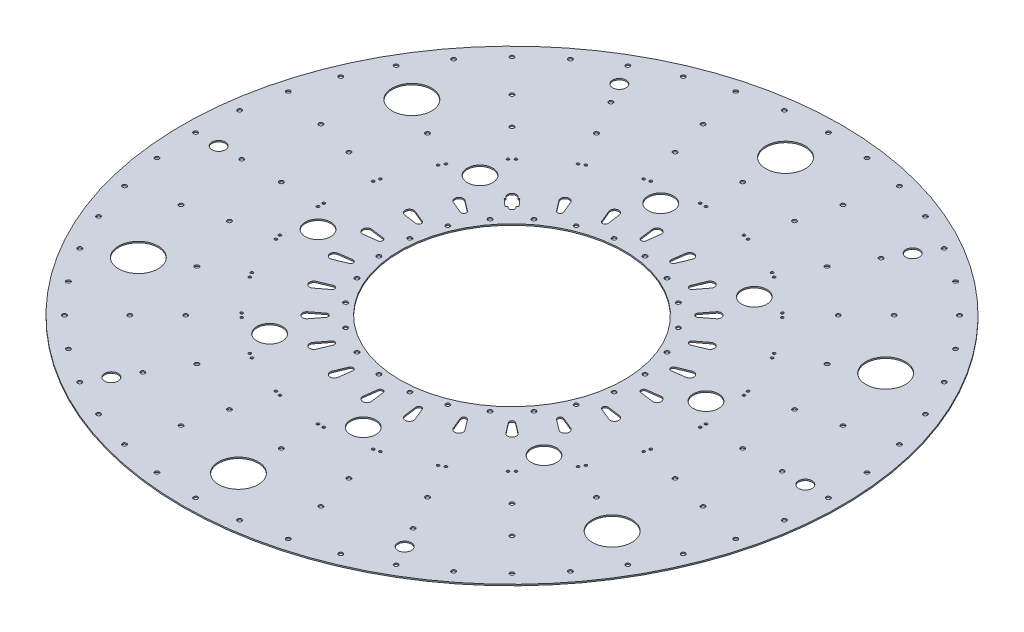
SolidWorks part; units mm, degrees
ref_plane "Front Plane" through (0, 0, 0) normal (0, 0, 1) x (1, 0, 0)
ref_plane "Top Plane" through (0, 0, 0) normal (0, 1, 0) x (1, 0, 0)
ref_plane "Right Plane" through (0, 0, 0) normal (1, 0, 0) x (0, 0, -1)
sketch "Sketch2" plane through (0, 0, 0) normal (0, 1, 0) x (1, 0, 0)
  line L0 (0, 0) -> (0, 231.6511) construction
  line L1 (-5.5, 109.8624) -> (-5, 99.8749) construction
  line L2 (5.5, 109.8624) -> (5, 99.8749) construction
  line L3 (-4.1887, 108.6693) -> (-3.8137, 101.1782) construction
  line L4 (4.1887, 108.6693) -> (3.8137, 101.1782) construction
  line L5 (24.0797, 106.0506) -> (22.5031, 98.7176) construction
  line L6 (32.1717, 103.8824) -> (29.8706, 96.7435) construction
  line L7 (50.7071, 96.2047) -> (47.2863, 89.5297) construction
  line L8 (57.9622, 92.016) -> (53.8918, 85.716) construction
  line L9 (73.8789, 79.8027) -> (68.8471, 74.2404) construction
  line L10 (79.8027, 73.8789) -> (74.2404, 68.8471) construction
  line L11 (92.016, 57.9622) -> (85.716, 53.8918) construction
  line L12 (96.2047, 50.7071) -> (89.5297, 47.2863) construction
  line L13 (103.8824, 32.1717) -> (96.7435, 29.8706) construction
  line L14 (106.0506, 24.0797) -> (98.7176, 22.5031) construction
  line L15 (108.6693, 4.1887) -> (101.1782, 3.8137) construction
  line L16 (108.6693, -4.1887) -> (101.1782, -3.8137) construction
  line L17 (106.0506, -24.0797) -> (98.7176, -22.5031) construction
  line L18 (103.8824, -32.1717) -> (96.7435, -29.8706) construction
  line L19 (96.2047, -50.7071) -> (89.5297, -47.2863) construction
  line L20 (92.016, -57.9622) -> (85.716, -53.8918) construction
  line L21 (79.8027, -73.8789) -> (74.2404, -68.8471) construction
  line L22 (73.8789, -79.8027) -> (68.8471, -74.2404) construction
  line L23 (57.9622, -92.016) -> (53.8918, -85.716) construction
  line L24 (50.7071, -96.2047) -> (47.2863, -89.5297) construction
  line L25 (32.1717, -103.8824) -> (29.8706, -96.7435) construction
  line L26 (24.0797, -106.0506) -> (22.5031, -98.7176) construction
  line L27 (4.1887, -108.6693) -> (3.8137, -101.1782) construction
  line L28 (-4.1887, -108.6693) -> (-3.8137, -101.1782) construction
  line L29 (-24.0797, -106.0506) -> (-22.5031, -98.7176) construction
  line L30 (-32.1717, -103.8824) -> (-29.8706, -96.7435) construction
  line L31 (-50.7071, -96.2047) -> (-47.2863, -89.5297) construction
  line L32 (-57.9622, -92.016) -> (-53.8918, -85.716) construction
  line L33 (-73.8789, -79.8027) -> (-68.8471, -74.2404) construction
  line L34 (-79.8027, -73.8789) -> (-74.2404, -68.8471) construction
  line L35 (-92.016, -57.9622) -> (-85.716, -53.8918) construction
  line L36 (-96.2047, -50.7071) -> (-89.5297, -47.2863) construction
  line L37 (-103.8824, -32.1717) -> (-96.7435, -29.8706) construction
  line L38 (-106.0506, -24.0797) -> (-98.7176, -22.5031) construction
  line L39 (-108.6693, -4.1887) -> (-101.1782, -3.8137) construction
  line L40 (-108.6693, 4.1887) -> (-101.1782, 3.8137) construction
  line L41 (-106.0506, 24.0797) -> (-98.7176, 22.5031) construction
  line L42 (-103.8824, 32.1717) -> (-96.7435, 29.8706) construction
  line L43 (-96.2047, 50.7071) -> (-89.5297, 47.2863) construction
  line L44 (-92.016, 57.9622) -> (-85.716, 53.8918) construction
  line L45 (-79.8027, 73.8789) -> (-74.2404, 68.8471)
  line L46 (-73.8789, 79.8027) -> (-68.8471, 74.2404)
  line L47 (-57.9622, 92.016) -> (-53.8918, 85.716) construction
  line L48 (-50.7071, 96.2047) -> (-47.2863, 89.5297) construction
  line L49 (-32.1717, 103.8824) -> (-29.8706, 96.7435) construction
  line L50 (-24.0797, 106.0506) -> (-22.5031, 98.7176) construction
  line L51 (0, 0) -> (192.6907, 111.25) construction
  line L52 (-45, -77.9423) -> (-80.1604, -138.8419) construction
  line L53 (3.277, 109.5687) -> (1.9829, 99.7391)
  line L54 (-3.277, 109.5687) -> (-1.9829, 99.7391)
  line L55 (31.5238, 104.9871) -> (27.7297, 95.8273)
  line L56 (25.1931, 106.6834) -> (23.899, 96.8538)
  line L57 (57.6223, 93.2508) -> (51.5868, 85.3851)
  line L58 (51.9464, 96.5278) -> (48.1523, 87.368)
  line L59 (79.7939, 75.1596) -> (71.9283, 69.1241)
  line L60 (75.1596, 79.7939) -> (69.1241, 71.9283)
  line L61 (96.5278, 51.9464) -> (87.368, 48.1523)
  line L62 (93.2508, 57.6223) -> (85.3851, 51.5868)
  line L63 (106.6834, 25.1931) -> (96.8538, 23.899)
  line L64 (104.9871, 31.5238) -> (95.8273, 27.7297)
  line L65 (109.5687, -3.277) -> (99.7391, -1.9829)
  line L66 (109.5687, 3.277) -> (99.7391, 1.9829)
  line L67 (104.9871, -31.5238) -> (95.8273, -27.7297)
  line L68 (106.6834, -25.1931) -> (96.8538, -23.899)
  line L69 (93.2508, -57.6223) -> (85.3851, -51.5868)
  line L70 (96.5278, -51.9464) -> (87.368, -48.1523)
  line L71 (75.1596, -79.7939) -> (69.1241, -71.9283)
  line L72 (79.7939, -75.1596) -> (71.9283, -69.1241)
  line L73 (51.9464, -96.5278) -> (48.1523, -87.368)
  line L74 (57.6223, -93.2508) -> (51.5868, -85.3851)
  line L75 (25.1931, -106.6834) -> (23.899, -96.8538)
  line L76 (31.5238, -104.9871) -> (27.7297, -95.8273)
  line L77 (-3.277, -109.5687) -> (-1.9829, -99.7391)
  line L78 (3.277, -109.5687) -> (1.9829, -99.7391)
  line L79 (-31.5238, -104.9871) -> (-27.7297, -95.8273)
  line L80 (-25.1931, -106.6834) -> (-23.899, -96.8538)
  line L81 (-57.6223, -93.2508) -> (-51.5868, -85.3851)
  line L82 (-51.9464, -96.5278) -> (-48.1523, -87.368)
  line L83 (-79.7939, -75.1596) -> (-71.9283, -69.1241)
  line L84 (-75.1596, -79.7939) -> (-69.1241, -71.9283)
  line L85 (-96.5278, -51.9464) -> (-87.368, -48.1523)
  line L86 (-93.2508, -57.6223) -> (-85.3851, -51.5868)
  line L87 (-106.6834, -25.1931) -> (-96.8538, -23.899)
  line L88 (-104.9871, -31.5238) -> (-95.8273, -27.7297)
  line L89 (-109.5687, 3.277) -> (-99.7391, 1.9829)
  line L90 (-109.5687, -3.277) -> (-99.7391, -1.9829)
  line L91 (-104.9871, 31.5238) -> (-95.8273, 27.7297)
  line L92 (-106.6834, 25.1931) -> (-96.8538, 23.899)
  line L93 (-93.2508, 57.6223) -> (-85.3851, 51.5868)
  line L94 (-96.5278, 51.9464) -> (-87.368, 48.1523)
  line L95 (-75.1596, 79.7939) -> (-69.1241, 71.9283)
  line L96 (-79.7939, 75.1596) -> (-71.9283, 69.1241)
  line L97 (-51.9464, 96.5278) -> (-48.1523, 87.368)
  line L98 (-57.6223, 93.2508) -> (-51.5868, 85.3851)
  line L99 (-25.1931, 106.6834) -> (-23.899, 96.8538)
  line L100 (-31.5238, 104.9871) -> (-27.7297, 95.8273)
  line L101 (0, 0) -> (0, 90) construction
  line L102 (0, 0) -> (-11.7474, 89.23) construction
  circle A0 centre (0, 0) radius 250 construction
  circle A1 centre (0, 0) radius 145 construction
  arc A2 (5.5, 109.8624) -> (-5.5, 109.8624) centre (0, 0) ccw construction
  arc A3 (5, 99.8749) -> (-5, 99.8749) centre (0, 0) ccw construction
  circle A4 centre (0, 0) radius 95 construction
  arc A5 (-5, 99.8749) -> (5, 99.8749) centre (0, 0) ccw construction
  arc A6 (-5.5, 109.8624) -> (5.5, 109.8624) centre (0, 0) ccw construction
  arc A7 (3.8137, 101.1782) -> (-3.8137, 101.1782) centre (0, 0) ccw construction
  arc A8 (4.1887, 108.6693) -> (-4.1887, 108.6693) centre (0, 0) ccw construction
  arc A9 (29.8706, 96.7435) -> (22.5031, 98.7176) centre (0, 0) ccw construction
  arc A10 (32.1717, 103.8824) -> (24.0797, 106.0506) centre (0, 0) ccw construction
  arc A11 (53.8918, 85.716) -> (47.2863, 89.5297) centre (0, 0) ccw construction
  arc A12 (57.9622, 92.016) -> (50.7071, 96.2047) centre (0, 0) ccw construction
  arc A13 (74.2404, 68.8471) -> (68.8471, 74.2404) centre (0, 0) ccw construction
  arc A14 (79.8027, 73.8789) -> (73.8789, 79.8027) centre (0, 0) ccw construction
  arc A15 (89.5297, 47.2863) -> (85.716, 53.8918) centre (0, 0) ccw construction
  arc A16 (96.2047, 50.7071) -> (92.016, 57.9622) centre (0, 0) ccw construction
  arc A17 (98.7176, 22.5031) -> (96.7435, 29.8706) centre (0, 0) ccw construction
  arc A18 (106.0506, 24.0797) -> (103.8824, 32.1717) centre (0, 0) ccw construction
  arc A19 (101.1782, -3.8137) -> (101.1782, 3.8137) centre (0, 0) ccw construction
  arc A20 (108.6693, -4.1887) -> (108.6693, 4.1887) centre (0, 0) ccw construction
  arc A21 (96.7435, -29.8706) -> (98.7176, -22.5031) centre (0, 0) ccw construction
  arc A22 (103.8824, -32.1717) -> (106.0506, -24.0797) centre (0, 0) ccw construction
  circle A23 centre (0, 240) radius 1.6
  circle A31 centre (0, 0) radius 75.5
  circle A32 centre (0, 90) radius 1.6 construction
  circle A33 centre (0, 40) radius 1.6 construction
  circle A34 centre (10.3528, 38.637) radius 1.6 construction
  circle A35 centre (23.2937, 86.9333) radius 1.6 construction
  circle A36 centre (20, 34.641) radius 1.6 construction
  circle A37 centre (45, 77.9423) radius 1.6 construction
  circle A38 centre (28.2843, 28.2843) radius 1.6 construction
  circle A39 centre (63.6396, 63.6396) radius 1.6 construction
  circle A40 centre (34.641, 20) radius 1.6 construction
  circle A41 centre (77.9423, 45) radius 1.6 construction
  circle A42 centre (38.637, 10.3528) radius 1.6 construction
  circle A43 centre (86.9333, 23.2937) radius 1.6 construction
  circle A44 centre (40, 0) radius 1.6 construction
  circle A45 centre (90, 0) radius 1.6 construction
  circle A46 centre (38.637, -10.3528) radius 1.6 construction
  circle A47 centre (86.9333, -23.2937) radius 1.6 construction
  circle A48 centre (231.8222, -62.1166) radius 1.6 [skipped]
  circle A49 centre (62.1166, 231.8222) radius 1.6 [skipped]
  circle A50 centre (120, 207.8461) radius 1.6 [skipped]
  circle A51 centre (240, 0) radius 1.6 [skipped]
  circle A52 centre (231.8222, 62.1166) radius 1.6 [skipped]
  circle A53 centre (169.7056, 169.7056) radius 1.6 [skipped]
  circle A54 centre (207.8461, 120) radius 1.6 [skipped]
  circle A55 centre (31.3263, 237.9468) radius 1.6
  circle A56 centre (62.1166, 231.8222) radius 1.6
  circle A57 centre (91.844, 221.7311) radius 1.6
  circle A58 centre (120, 207.8461) radius 1.6
  circle A59 centre (146.1027, 190.4048) radius 1.6
  arc A60 (85.716, -53.8918) -> (89.5297, -47.2863) centre (0, 0) ccw construction
  arc A61 (92.016, -57.9622) -> (96.2047, -50.7071) centre (0, 0) ccw construction
  circle A62 centre (207.8461, -120) radius 1.6
  circle A63 centre (34.641, -20) radius 1.6 construction
  circle A64 centre (77.9423, -45) radius 1.6 construction
  arc A65 (68.8471, -74.2404) -> (74.2404, -68.8471) centre (0, 0) ccw construction
  arc A66 (73.8789, -79.8027) -> (79.8027, -73.8789) centre (0, 0) ccw construction
  circle A67 centre (169.7056, -169.7056) radius 1.6
  circle A68 centre (28.2843, -28.2843) radius 1.6 construction
  circle A69 centre (63.6396, -63.6396) radius 1.6 construction
  arc A70 (47.2863, -89.5297) -> (53.8918, -85.716) centre (0, 0) ccw construction
  arc A71 (50.7071, -96.2047) -> (57.9622, -92.016) centre (0, 0) ccw construction
  circle A72 centre (120, -207.8461) radius 1.6
  circle A73 centre (20, -34.641) radius 1.6 construction
  circle A74 centre (45, -77.9423) radius 1.6 construction
  arc A75 (22.5031, -98.7176) -> (29.8706, -96.7435) centre (0, 0) ccw construction
  arc A76 (24.0797, -106.0506) -> (32.1717, -103.8824) centre (0, 0) ccw construction
  circle A77 centre (62.1166, -231.8222) radius 1.6
  circle A78 centre (10.3528, -38.637) radius 1.6 construction
  circle A79 centre (23.2937, -86.9333) radius 1.6 construction
  arc A80 (-3.8137, -101.1782) -> (3.8137, -101.1782) centre (0, 0) ccw construction
  arc A81 (-4.1887, -108.6693) -> (4.1887, -108.6693) centre (0, 0) ccw construction
  circle A82 centre (0, -240) radius 1.6
  circle A83 centre (0, -40) radius 1.6 construction
  circle A84 centre (0, -90) radius 1.6 construction
  arc A85 (-29.8706, -96.7435) -> (-22.5031, -98.7176) centre (0, 0) ccw construction
  arc A86 (-32.1717, -103.8824) -> (-24.0797, -106.0506) centre (0, 0) ccw construction
  circle A87 centre (-62.1166, -231.8222) radius 1.6
  circle A88 centre (-10.3528, -38.637) radius 1.6 construction
  circle A89 centre (-23.2937, -86.9333) radius 1.6 construction
  arc A90 (-53.8918, -85.716) -> (-47.2863, -89.5297) centre (0, 0) ccw construction
  arc A91 (-57.9622, -92.016) -> (-50.7071, -96.2047) centre (0, 0) ccw construction
  circle A92 centre (-120, -207.8461) radius 1.6
  circle A93 centre (-20, -34.641) radius 1.6 construction
  circle A94 centre (-45, -77.9423) radius 1.6 construction
  arc A95 (-74.2404, -68.8471) -> (-68.8471, -74.2404) centre (0, 0) ccw construction
  arc A96 (-79.8027, -73.8789) -> (-73.8789, -79.8027) centre (0, 0) ccw construction
  circle A97 centre (-169.7056, -169.7056) radius 1.6
  circle A98 centre (-28.2843, -28.2843) radius 1.6 construction
  circle A99 centre (-63.6396, -63.6396) radius 1.6 construction
  arc A100 (-89.5297, -47.2863) -> (-85.716, -53.8918) centre (0, 0) ccw construction
  arc A101 (-96.2047, -50.7071) -> (-92.016, -57.9622) centre (0, 0) ccw construction
  circle A102 centre (-207.8461, -120) radius 1.6
  circle A103 centre (-34.641, -20) radius 1.6 construction
  circle A104 centre (-77.9423, -45) radius 1.6 construction
  arc A105 (-98.7176, -22.5031) -> (-96.7435, -29.8706) centre (0, 0) ccw construction
  arc A106 (-106.0506, -24.0797) -> (-103.8824, -32.1717) centre (0, 0) ccw construction
  circle A107 centre (-231.8222, -62.1166) radius 1.6
  circle A108 centre (-38.637, -10.3528) radius 1.6 construction
  circle A109 centre (-86.9333, -23.2937) radius 1.6 construction
  arc A110 (-101.1782, 3.8137) -> (-101.1782, -3.8137) centre (0, 0) ccw construction
  arc A111 (-108.6693, 4.1887) -> (-108.6693, -4.1887) centre (0, 0) ccw construction
  circle A112 centre (-240, 0) radius 1.6
  circle A113 centre (-40, 0) radius 1.6 construction
  circle A114 centre (-90, 0) radius 1.6 construction
  arc A115 (-96.7435, 29.8706) -> (-98.7176, 22.5031) centre (0, 0) ccw construction
  arc A116 (-103.8824, 32.1717) -> (-106.0506, 24.0797) centre (0, 0) ccw construction
  circle A117 centre (-231.8222, 62.1166) radius 1.6
  circle A118 centre (-38.637, 10.3528) radius 1.6 construction
  circle A119 centre (-86.9333, 23.2937) radius 1.6 construction
  arc A120 (-85.716, 53.8918) -> (-89.5297, 47.2863) centre (0, 0) ccw construction
  arc A121 (-92.016, 57.9622) -> (-96.2047, 50.7071) centre (0, 0) ccw construction
  circle A122 centre (-207.8461, 120) radius 1.6
  circle A123 centre (-34.641, 20) radius 1.6 construction
  circle A124 centre (-77.9423, 45) radius 1.6 construction
  arc A125 (-68.8471, 74.2404) -> (-74.2404, 68.8471) centre (0, 0) ccw
  arc A126 (-73.8789, 79.8027) -> (-79.8027, 73.8789) centre (0, 0) ccw
  circle A127 centre (-169.7056, 169.7056) radius 1.6
  circle A128 centre (-28.2843, 28.2843) radius 1.6 construction
  circle A129 centre (-63.6396, 63.6396) radius 1.6 construction
  arc A130 (-47.2863, 89.5297) -> (-53.8918, 85.716) centre (0, 0) ccw construction
  arc A131 (-50.7071, 96.2047) -> (-57.9622, 92.016) centre (0, 0) ccw construction
  circle A132 centre (-120, 207.8461) radius 1.6
  circle A133 centre (-20, 34.641) radius 1.6 construction
  circle A134 centre (-45, 77.9423) radius 1.6 construction
  arc A135 (-22.5031, 98.7176) -> (-29.8706, 96.7435) centre (0, 0) ccw construction
  arc A136 (-24.0797, 106.0506) -> (-32.1717, 103.8824) centre (0, 0) ccw construction
  circle A137 centre (-62.1166, 231.8222) radius 1.6
  circle A138 centre (-10.3528, 38.637) radius 1.6 construction
  circle A139 centre (-23.2937, 86.9333) radius 1.6 construction
  circle A140 centre (169.7056, 169.7056) radius 1.6
  circle A141 centre (190.4048, 146.1027) radius 1.6
  circle A142 centre (207.8461, 120) radius 1.6
  circle A143 centre (221.7311, 91.844) radius 1.6
  circle A144 centre (231.8222, 62.1166) radius 1.6
  circle A145 centre (237.9468, 31.3263) radius 1.6
  circle A146 centre (240, 0) radius 1.6
  circle A147 centre (237.9468, -31.3263) radius 1.6
  circle A148 centre (231.8222, -62.1166) radius 1.6
  circle A149 centre (221.7311, -91.844) radius 1.6
  circle A150 centre (207.8461, -120) radius 1.6
  circle A151 centre (190.4048, -146.1027) radius 1.6
  circle A152 centre (169.7056, -169.7056) radius 1.6
  circle A153 centre (146.1027, -190.4048) radius 1.6
  circle A154 centre (120, -207.8461) radius 1.6
  circle A155 centre (91.844, -221.7311) radius 1.6
  circle A156 centre (62.1166, -231.8222) radius 1.6
  circle A157 centre (31.3263, -237.9468) radius 1.6
  circle A158 centre (0, -240) radius 1.6
  circle A159 centre (-31.3263, -237.9468) radius 1.6
  circle A160 centre (-62.1166, -231.8222) radius 1.6
  circle A161 centre (-91.844, -221.7311) radius 1.6
  circle A162 centre (-120, -207.8461) radius 1.6
  circle A163 centre (-146.1027, -190.4048) radius 1.6
  circle A164 centre (-169.7056, -169.7056) radius 1.6
  circle A165 centre (-190.4048, -146.1027) radius 1.6
  circle A166 centre (-207.8461, -120) radius 1.6
  circle A167 centre (-221.7311, -91.844) radius 1.6
  circle A168 centre (-231.8222, -62.1166) radius 1.6
  circle A169 centre (-237.9468, -31.3263) radius 1.6
  circle A170 centre (-240, 0) radius 1.6
  circle A171 centre (-237.9468, 31.3263) radius 1.6
  circle A172 centre (-231.8222, 62.1166) radius 1.6
  circle A173 centre (-221.7311, 91.844) radius 1.6
  circle A174 centre (-207.8461, 120) radius 1.6
  circle A175 centre (-190.4048, 146.1027) radius 1.6
  circle A176 centre (-169.7056, 169.7056) radius 1.6
  circle A177 centre (-146.1027, 190.4048) radius 1.6
  circle A178 centre (-120, 207.8461) radius 1.6
  circle A179 centre (-91.844, 221.7311) radius 1.6
  circle A180 centre (-62.1166, 231.8222) radius 1.6
  circle A181 centre (-31.3263, 237.9468) radius 1.6
  circle A182 centre (0, 0) radius 222.5 construction
  circle A183 centre (0, 222.5) radius 4.1 construction
  circle A184 centre (192.6907, 111.25) radius 4.1 construction
  circle A185 centre (192.6907, -111.25) radius 4.1 construction
  circle A186 centre (0, -222.5) radius 4.1 construction
  circle A187 centre (-192.6907, -111.25) radius 4.1 construction
  circle A188 centre (-192.6907, 111.25) radius 4.1 construction
  circle A189 centre (0, 0) radius 250
  circle A190 centre (0, 0) radius 175 construction
  circle A191 centre (0, 175) radius 1.6
  circle A192 centre (45.2933, 169.037) radius 1.6
  circle A193 centre (87.5, 151.5544) radius 1.6
  circle A194 centre (123.7437, 123.7437) radius 1.6
  circle A195 centre (151.5544, 87.5) radius 1.6
  circle A196 centre (169.037, 45.2933) radius 1.6
  circle A197 centre (175, 0) radius 1.6
  circle A198 centre (169.037, -45.2933) radius 1.6
  circle A199 centre (151.5544, -87.5) radius 1.6
  circle A200 centre (123.7437, -123.7437) radius 1.6
  circle A201 centre (87.5, -151.5544) radius 1.6
  circle A202 centre (45.2933, -169.037) radius 1.6
  circle A203 centre (0, -175) radius 1.6
  circle A204 centre (-45.2933, -169.037) radius 1.6
  circle A205 centre (-87.5, -151.5544) radius 1.6
  circle A206 centre (-123.7437, -123.7437) radius 1.6
  circle A207 centre (-151.5544, -87.5) radius 1.6
  circle A208 centre (-169.037, -45.2933) radius 1.6
  circle A209 centre (-175, 0) radius 1.6
  circle A210 centre (-169.037, 45.2933) radius 1.6
  circle A211 centre (-151.5544, 87.5) radius 1.6
  circle A212 centre (-123.7437, 123.7437) radius 1.6
  circle A213 centre (-87.5, 151.5544) radius 1.6
  circle A214 centre (-45.2933, 169.037) radius 1.6
  circle A215 centre (0, -207.5) radius 15
  circle A216 centre (0, 0) radius 207.5 construction
  circle A217 centre (-179.7003, -103.75) radius 15
  circle A218 centre (-179.7003, 103.75) radius 15
  circle A219 centre (0, 207.5) radius 15
  circle A220 centre (179.7003, 103.75) radius 15
  circle A221 centre (179.7003, -103.75) radius 15
  circle A222 centre (-74.373, -124.4735) radius 1
  circle A223 centre (-70.6108, -126.6457) radius 1
  circle A224 centre (-104.0549, -100.9831) radius 1
  circle A225 centre (-100.9831, -104.0549) radius 1
  circle A226 centre (-126.6457, -70.6108) radius 1
  circle A227 centre (-124.4735, -74.373) radius 1
  circle A228 centre (-140.6057, -35.4264) radius 1
  circle A229 centre (-139.4813, -39.6227) radius 1
  circle A230 centre (-144.9837, 2.1721) radius 1
  circle A231 centre (-144.9837, -2.1721) radius 1
  circle A232 centre (-139.4813, 39.6227) radius 1
  circle A233 centre (-140.6057, 35.4264) radius 1
  circle A234 centre (-124.4735, 74.373) radius 1
  circle A235 centre (-126.6457, 70.6108) radius 1
  circle A236 centre (-100.9831, 104.0549) radius 1
  circle A237 centre (-104.0549, 100.9831) radius 1
  circle A238 centre (-70.6108, 126.6457) radius 1
  circle A239 centre (-74.373, 124.4735) radius 1
  circle A240 centre (-35.4264, 140.6057) radius 1
  circle A241 centre (-39.6227, 139.4813) radius 1
  circle A242 centre (2.1721, 144.9837) radius 1
  circle A243 centre (-2.1721, 144.9837) radius 1
  circle A244 centre (39.6227, 139.4813) radius 1
  circle A245 centre (35.4264, 140.6057) radius 1
  circle A246 centre (74.373, 124.4735) radius 1
  circle A247 centre (70.6108, 126.6457) radius 1
  circle A248 centre (104.0549, 100.9831) radius 1
  circle A249 centre (100.9831, 104.0549) radius 1
  circle A250 centre (126.6457, 70.6108) radius 1
  circle A251 centre (124.4735, 74.373) radius 1
  circle A252 centre (140.6057, 35.4264) radius 1
  circle A253 centre (139.4813, 39.6227) radius 1
  circle A254 centre (144.9837, -2.1721) radius 1
  circle A255 centre (144.9837, 2.1721) radius 1
  circle A256 centre (139.4813, -39.6227) radius 1
  circle A257 centre (140.6057, -35.4264) radius 1
  circle A258 centre (124.4735, -74.373) radius 1
  circle A259 centre (126.6457, -70.6108) radius 1
  circle A260 centre (100.9831, -104.0549) radius 1
  circle A261 centre (104.0549, -100.9831) radius 1
  circle A262 centre (70.6108, -126.6457) radius 1
  circle A263 centre (74.373, -124.4735) radius 1
  circle A264 centre (35.4264, -140.6057) radius 1
  circle A265 centre (39.6227, -139.4813) radius 1
  circle A266 centre (-2.1721, -144.9837) radius 1
  circle A267 centre (2.1721, -144.9837) radius 1
  circle A268 centre (-39.6227, -139.4813) radius 1
  circle A269 centre (-35.4264, -140.6057) radius 1
  circle A270 centre (222.5, 0) radius 5.1
  circle A271 centre (111.25, -192.6907) radius 5.1
  circle A272 centre (-111.25, -192.6907) radius 5.1
  circle A273 centre (-222.5, 0) radius 5.1
  circle A274 centre (-111.25, 192.6907) radius 5.1
  circle A275 centre (111.25, 192.6907) radius 5.1
  arc A276 (-1.9829, 99.7391) -> (1.9829, 99.7391) centre (0, 100.0001) ccw
  arc A277 (3.277, 109.5687) -> (-3.277, 109.5687) centre (0, 110.0001) ccw
  arc A278 (23.899, 96.8538) -> (27.7297, 95.8273) centre (25.8819, 96.5927) ccw
  arc A279 (31.5238, 104.9871) -> (25.1931, 106.6834) centre (28.4701, 106.252) ccw
  arc A280 (48.1523, 87.368) -> (51.5868, 85.3851) centre (50.0001, 86.6026) ccw
  arc A281 (57.6223, 93.2508) -> (51.9464, 96.5278) centre (55.0001, 95.2629) ccw
  arc A282 (69.1241, 71.9283) -> (71.9283, 69.1241) centre (70.7108, 70.7108) ccw
  arc A283 (79.7939, 75.1596) -> (75.1596, 79.7939) centre (77.7818, 77.7818) ccw
  arc A284 (85.3851, 51.5868) -> (87.368, 48.1523) centre (86.6026, 50.0001) ccw
  arc A285 (96.5278, 51.9464) -> (93.2508, 57.6223) centre (95.2629, 55.0001) ccw
  arc A286 (95.8273, 27.7297) -> (96.8538, 23.899) centre (96.5927, 25.8819) ccw
  arc A287 (106.6834, 25.1931) -> (104.9871, 31.5238) centre (106.252, 28.4701) ccw
  arc A288 (99.7391, 1.9829) -> (99.7391, -1.9829) centre (100.0001, 0) ccw
  arc A289 (109.5687, -3.277) -> (109.5687, 3.277) centre (110.0001, 0) ccw
  arc A290 (96.8538, -23.899) -> (95.8273, -27.7297) centre (96.5927, -25.8819) ccw
  arc A291 (104.9871, -31.5238) -> (106.6834, -25.1931) centre (106.252, -28.4701) ccw
  arc A292 (87.368, -48.1523) -> (85.3851, -51.5868) centre (86.6026, -50.0001) ccw
  arc A293 (93.2508, -57.6223) -> (96.5278, -51.9464) centre (95.2629, -55.0001) ccw
  arc A294 (71.9283, -69.1241) -> (69.1241, -71.9283) centre (70.7108, -70.7108) ccw
  arc A295 (75.1596, -79.7939) -> (79.7939, -75.1596) centre (77.7818, -77.7818) ccw
  arc A296 (51.5868, -85.3851) -> (48.1523, -87.368) centre (50.0001, -86.6026) ccw
  arc A297 (51.9464, -96.5278) -> (57.6223, -93.2508) centre (55.0001, -95.2629) ccw
  arc A298 (27.7297, -95.8273) -> (23.899, -96.8538) centre (25.8819, -96.5927) ccw
  arc A299 (25.1931, -106.6834) -> (31.5238, -104.9871) centre (28.4701, -106.252) ccw
  arc A300 (1.9829, -99.7391) -> (-1.9829, -99.7391) centre (0, -100.0001) ccw
  arc A301 (-3.277, -109.5687) -> (3.277, -109.5687) centre (0, -110.0001) ccw
  arc A302 (-23.899, -96.8538) -> (-27.7297, -95.8273) centre (-25.8819, -96.5927) ccw
  arc A303 (-31.5238, -104.9871) -> (-25.1931, -106.6834) centre (-28.4701, -106.252) ccw
  arc A304 (-48.1523, -87.368) -> (-51.5868, -85.3851) centre (-50.0001, -86.6026) ccw
  arc A305 (-57.6223, -93.2508) -> (-51.9464, -96.5278) centre (-55.0001, -95.2629) ccw
  arc A306 (-69.1241, -71.9283) -> (-71.9283, -69.1241) centre (-70.7108, -70.7108) ccw
  arc A307 (-79.7939, -75.1596) -> (-75.1596, -79.7939) centre (-77.7818, -77.7818) ccw
  arc A308 (-85.3851, -51.5868) -> (-87.368, -48.1523) centre (-86.6026, -50.0001) ccw
  arc A309 (-96.5278, -51.9464) -> (-93.2508, -57.6223) centre (-95.2629, -55.0001) ccw
  arc A310 (-95.8273, -27.7297) -> (-96.8538, -23.899) centre (-96.5927, -25.8819) ccw
  arc A311 (-106.6834, -25.1931) -> (-104.9871, -31.5238) centre (-106.252, -28.4701) ccw
  arc A312 (-99.7391, -1.9829) -> (-99.7391, 1.9829) centre (-100.0001, 0) ccw
  arc A313 (-109.5687, 3.277) -> (-109.5687, -3.277) centre (-110.0001, 0) ccw
  arc A314 (-96.8538, 23.899) -> (-95.8273, 27.7297) centre (-96.5927, 25.8819) ccw
  arc A315 (-104.9871, 31.5238) -> (-106.6834, 25.1931) centre (-106.252, 28.4701) ccw
  arc A316 (-87.368, 48.1523) -> (-85.3851, 51.5868) centre (-86.6026, 50.0001) ccw
  arc A317 (-93.2508, 57.6223) -> (-96.5278, 51.9464) centre (-95.2629, 55.0001) ccw
  arc A318 (-71.9283, 69.1241) -> (-69.1241, 71.9283) centre (-70.7108, 70.7108) ccw
  arc A319 (-75.1596, 79.7939) -> (-79.7939, 75.1596) centre (-77.7818, 77.7818) ccw
  arc A320 (-51.5868, 85.3851) -> (-48.1523, 87.368) centre (-50.0001, 86.6026) ccw
  arc A321 (-51.9464, 96.5278) -> (-57.6223, 93.2508) centre (-55.0001, 95.2629) ccw
  arc A322 (-27.7297, 95.8273) -> (-23.899, 96.8538) centre (-25.8819, 96.5927) ccw
  arc A323 (-25.1931, 106.6834) -> (-31.5238, 104.9871) centre (-28.4701, 106.252) ccw
  circle A324 centre (-104.0549, 79.7939) radius 9.6193
  circle A325 centre (-17.1551, 130.0008) radius 9.6193
  circle A326 centre (79.7939, 104.0549) radius 9.6193
  circle A327 centre (130.0008, 17.1551) radius 9.6193
  circle A328 centre (104.0549, -79.7939) radius 9.6193
  circle A329 centre (17.1551, -130.0008) radius 9.6193
  circle A330 centre (-79.7939, -104.0549) radius 9.6193
  circle A331 centre (-130.0008, -17.1551) radius 9.6193
  circle A332 centre (-11.7474, 89.23) radius 1.6
  circle A333 centre (11.7474, 89.23) radius 1.6
  circle A334 centre (34.4415, 83.1492) radius 1.6
  circle A335 centre (54.7885, 71.4018) radius 1.6
  circle A336 centre (71.4018, 54.7885) radius 1.6
  circle A337 centre (83.1492, 34.4415) radius 1.6
  circle A338 centre (89.23, 11.7474) radius 1.6
  circle A339 centre (89.23, -11.7474) radius 1.6
  circle A340 centre (83.1492, -34.4415) radius 1.6
  circle A341 centre (71.4018, -54.7885) radius 1.6
  circle A342 centre (54.7885, -71.4018) radius 1.6
  circle A343 centre (34.4415, -83.1492) radius 1.6
  circle A344 centre (11.7474, -89.23) radius 1.6
  circle A345 centre (-11.7474, -89.23) radius 1.6
  circle A346 centre (-34.4415, -83.1492) radius 1.6
  circle A347 centre (-54.7885, -71.4018) radius 1.6
  circle A348 centre (-71.4018, -54.7885) radius 1.6
  circle A349 centre (-83.1492, -34.4415) radius 1.6
  circle A350 centre (-89.23, -11.7474) radius 1.6
  circle A351 centre (-89.23, 11.7474) radius 1.6
  circle A352 centre (-83.1492, 34.4415) radius 1.6
  circle A353 centre (-71.4018, 54.7885) radius 1.6
  circle A354 centre (-54.7885, 71.4018) radius 1.6
  circle A355 centre (-34.4415, 83.1492) radius 1.6
  circle A356 centre (-53.0579, 198.0148) radius 1.6
  circle A357 centre (-53.0579, 198.0148) radius 1.6
  circle A358 centre (0, 205) radius 1.6 construction
  circle A359 centre (53.0579, 198.0148) radius 1.6
  circle A360 centre (102.5, 177.5352) radius 1.6
  circle A361 centre (144.9569, 144.9569) radius 1.6
  circle A362 centre (177.5352, 102.5) radius 1.6 construction
  circle A363 centre (198.0148, 53.0579) radius 1.6
  circle A364 centre (205, 0) radius 1.6
  circle A365 centre (198.0148, -53.0579) radius 1.6
  circle A366 centre (177.5352, -102.5) radius 1.6 construction
  circle A367 centre (144.9569, -144.9569) radius 1.6
  circle A368 centre (102.5, -177.5352) radius 1.6
  circle A369 centre (53.0579, -198.0148) radius 1.6
  circle A370 centre (0, -205) radius 1.6 construction
  circle A371 centre (-53.0579, -198.0148) radius 1.6
  circle A372 centre (-102.5, -177.5352) radius 1.6
  circle A373 centre (-144.9569, -144.9569) radius 1.6
  circle A374 centre (-177.5352, -102.5) radius 1.6 construction
  circle A375 centre (-198.0148, -53.0579) radius 1.6
  circle A376 centre (-205, 0) radius 1.6
  circle A377 centre (-198.0148, 53.0579) radius 1.6
  circle A378 centre (-177.5352, 102.5) radius 1.6 construction
  circle A379 centre (-144.9569, 144.9569) radius 1.6
  circle A380 centre (-102.5, 177.5352) radius 1.6
  point P46 (0, 0)
  point P62 (0, 0)
  point P364 (0, 0)
  point P415 (0, 0)
  point P429 (0, 0)
  point P527 (0, 0)
  point P540 (0, 0)
  point P685 (0, 0)
  point P703 (0, 0)
  point P754 (0, 0)
  point P806 (0, 0)
  dimension "D1" = 500
  dimension "D2" = 290
  dimension "D3" = 220
  dimension "D4" = 200
  dimension "D5" = 190
  dimension "D9" = 3.2
  dimension "D11" = 151
  dimension "D12" = 50
  dimension "D14" = 3.2
  dimension "D16" = 445
  dimension "D17" = 8.2
  dimension "D20" = 500
  dimension "D21" = 350
  dimension "D22" = 3.2
  dimension "D24" = 415
  dimension "D25" = 30
  dimension "D27" = 2
  dimension "D29" = 222.5
  dimension "D30" = 10.2
  dimension "D33" = 8
  dimension "D38" = 3.2
  dimension "D6" = 10
  dimension "D7" = 1.25
  dimension "D10" = 240
  dimension "D13" = 40
  dimension "D15" = 48
  dimension "D19" = 60
  dimension "D35" = 7.5
  dimension "D36" = 90
  dimension "D39" = 24
  dimension "D8" = 24
  dimension "D18" = 6
  dimension "D23" = 24
  dimension "D26" = 6
  dimension "D28" = 24
  dimension "D31" = 6
  dimension "D32" = 24
  dimension "D34" = 2
  dimension "D37" = 24
extrude "Boss-Extrude1" add sketch "Sketch2" along normal mid plane 1 contours A0 A137 A136 L50 A135 L49 A132 A131 L48 A130 L47 A127 A126 L46 A125 L45 A121 L44 A120 L43 A117 A116 L42 A115 L41 A112 A111 L40 A110 L39 A107 A106 L38 A105 L37 A101 L36 region at (-242.9289, 0, 0)
sketch "Sketch3" plane through (0, 0.5, 0) normal (0, 1, 0) x (1, 0, 0)
  circle A0 centre (0, 0) radius 85
  dimension "D1" = 170
extrude "Cut-Extrude1" cut sketch "Sketch3" against normal through all both and the other way through all
